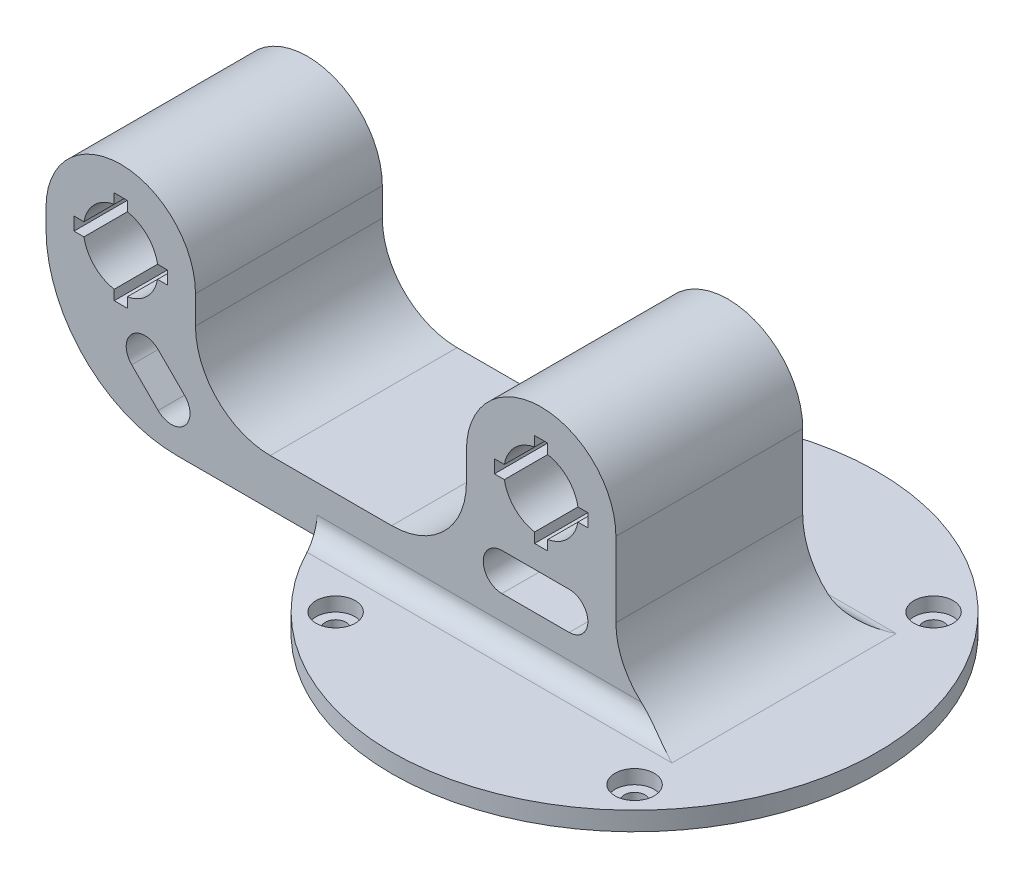
SolidWorks part; units mm, degrees
note: The reader was unsure of these and kept them because the rebuilt part matched: shared geometry of "Эскиз1<3>", "Эскиз1<4>", "Эскиз3<6>", "Эскиз3<7>", "Эскиз4<4>".
ref_plane "Спереди" through (0, 0, 0) normal (0, 0, 1) x (1, 0, 0)
ref_plane "Сверху" through (0, 0, 0) normal (0, 1, 0) x (1, 0, 0)
ref_plane "Справа" through (0, 0, 0) normal (1, 0, 0) x (0, 0, -1)
sketch "Эскиз1" plane through (0, 0, 0) normal (0, 1, 0) x (1, 0, 0)
  line L0 (-16, 0) -> (-16, 16) construction
  line L1 (0, -16) -> (16, -16) construction
  line L2 (-16, 16) -> (0, 16) construction
  line L3 (0, 16) -> (16, 16) construction
  line L4 (16, 16) -> (16, 0) construction
  line L5 (0, 16) -> (0, -16) construction
  line L6 (16, 0) -> (-16, 0) construction
  line L7 (16, 0) -> (16, -16) construction
  line L8 (-16, 0) -> (-16, -16) construction
  line L9 (-16, -16) -> (0, -16) construction
  circle A0 centre (0, 0) radius 24
  circle A1 centre (-16, 16) radius 1.1
  circle A2 centre (16, 16) radius 1.1
  circle A3 centre (16, -16) radius 1.1
  circle A4 centre (-16, -16) radius 1.1
  circle A5 centre (0, 0) radius 26
  dimension "D1" = 48
  dimension "D2" = 2
  dimension "D4" = 2
  dimension "D3" = 2
extrude "Бобышка-Вытянуть1" add sketch "Эскиз1" along normal blind 2 contours A5
extrude "Бобышка-Вытянуть2" add sketch "Эскиз1<3>" against normal blind 1 contours A0
sketch "Эскиз1<3>" plane through (0, 0, 0) normal (0, 1, 0) x (1, 0, 0) same geometry as "Эскиз1"
sketch "Эскиз2" plane through (0, -1, 0) normal (0, -1, 0) x (1, 0, 0)
extrude "Вырез-Вытянуть1" cut sketch "Эскиз1<4>" against normal through all both and the other way through all contours A1 | A4 | A3 | A2
sketch "Эскиз1<4>" plane through (0, 0, 0) normal (0, 1, 0) x (1, 0, 0) same geometry as "Эскиз1"
sketch "Эскиз3" plane through (0, 2, 0) normal (0, 1, 0) x (1, 0, 0)
  line L0 (-37, 10) -> (-53, 10)
  line L1 (8, 10) -> (-8, 10)
  line L2 (8, 10) -> (8, -10)
  line L3 (8, -10) -> (-8, -10)
  line L4 (-8, 10) -> (-8, -10)
  line L5 (0, -10) -> (0, 10) construction
  line L6 (8, 0) -> (-8, 0) construction
  line L7 (-37, 10) -> (-37, -10)
  line L8 (-37, -10) -> (-53, -10)
  line L9 (-53, 10) -> (-53, -10)
  line L10 (-45, -10) -> (-45, 10) construction
  line L11 (-37, 0) -> (-53, 0) construction
  line L12 (-37, -10) -> (-8, -10)
  line L13 (-37, 10) -> (-8, 10)
  circle A0 centre (-16, 16) radius 1.1 construction
  circle A1 centre (-16, -16) radius 1.1 construction
  circle A2 centre (16, -16) radius 1.1 construction
  circle A3 centre (16, 16) radius 1.1 construction
  circle A4 centre (-16, 16) radius 1.1
  circle A5 centre (-16, -16) radius 1.1
  circle A6 centre (16, -16) radius 1.1
  circle A7 centre (16, 16) radius 1.1
  circle A8 centre (16, 16) radius 2.1
  circle A9 centre (16, -16) radius 2.1
  circle A10 centre (-16, -16) radius 2.1
  circle A11 centre (-16, 16) radius 2.1
  point P20 (0, 0)
  point P26 (-45, 0)
  point P42 (-45, 0)
  circle M5 centre (0, 0) radius 26
  dimension "D2" = 4.2
  dimension "D3" = 20
  dimension "D4" = 16
  dimension "D5" = 2
  dimension "D6" = 45
  dimension "D7" = 16
  dimension "D8" = 0
  dimension "D1" = 1
extrude "Вырез-Вытянуть2" cut sketch "Эскиз3" against normal blind 1.5 contours A9 | A8 | A10 | A11
extrude "Бобышка-Вытянуть4" add sketch "Эскиз3<6>" along normal blind 24 contours L0 L9 L8 L7 | L1 L4 L3 L2
sketch "Эскиз3<6>" plane through (0, 2, 0) normal (0, 1, 0) x (1, 0, 0) same geometry as "Эскиз3"
extrude "Бобышка-Вытянуть5" add sketch "Эскиз3<7>" along normal blind 5 contours L13 L7 L12 M5 | L13 L12 L4 M5
sketch "Эскиз3<7>" plane through (0, 2, 0) normal (0, 1, 0) x (1, 0, 0) same geometry as "Эскиз3"
sketch "Эскиз4" plane through (0, 0, 10) normal (0, 0, 1) x (1, 0, 0)
  line L0 (-53, 26) -> (-53, 2) construction
  line L1 (8, 26) -> (8, 2) construction
  line L2 (-37, 7) -> (-8, 7) construction
  line L3 (-37, 26) -> (-37, 7) construction
  line L4 (-53, 2) -> (-24, 2) construction
  line L5 (-42.4142, 9.4142) -> (-39.5858, 6.5858) construction
  line L6 (0.7, 13) -> (-0.7, 13)
  line L7 (-4.2, 8.6) -> (3, 8.6) construction
  line L8 (-41, 10.8284) -> (-38.1716, 8)
  line L9 (-43.8284, 8) -> (-41, 5.1716)
  line L10 (0.7, 13) -> (0.7, 23)
  line L11 (-4.2, 10.6) -> (3, 10.6)
  line L12 (-4.2, 6.6) -> (3, 6.6)
  line L13 (0.7, 23) -> (-0.7, 23)
  line L14 (-0.7, 13) -> (-0.7, 23)
  line L15 (0, 23) -> (0, 13) construction
  line L16 (0.7, 18) -> (-0.7, 18) construction
  line L17 (5, 17.3) -> (-5, 17.3)
  line L18 (5, 17.3) -> (5, 18.7)
  line L19 (5, 18.7) -> (-5, 18.7)
  line L20 (-5, 17.3) -> (-5, 18.7)
  line L21 (0, 18.7) -> (0, 17.3) construction
  line L22 (5, 18) -> (-5, 18) construction
  line L24 (-44.3, 13) -> (-45.7, 13)
  line L25 (-44.3, 13) -> (-44.3, 23)
  line L26 (-44.3, 23) -> (-45.7, 23)
  line L27 (-45.7, 13) -> (-45.7, 23)
  line L28 (-45, 23) -> (-45, 13) construction
  line L29 (-44.3, 18) -> (-45.7, 18) construction
  line L30 (-40, 17.3) -> (-50, 17.3)
  line L31 (-40, 17.3) -> (-40, 18.7)
  line L32 (-40, 18.7) -> (-50, 18.7)
  line L33 (-50, 17.3) -> (-50, 18.7)
  line L34 (-45, 18.7) -> (-45, 17.3) construction
  line L35 (-40, 18) -> (-50, 18) construction
  circle A0 centre (-45, 18) radius 4
  circle A1 centre (0, 18) radius 4
  arc A2 (-53, 18) -> (-37, 18) centre (-45, 18) cw
  arc A3 (-8, 18) -> (8, 18) centre (0, 18) cw
  arc A4 (-39, 2) -> (-53, 16) centre (-39, 16) cw
  arc A5 (-4.2, 10.6) -> (-4.2, 6.6) centre (-4.2, 8.6) ccw
  arc A6 (-41, 10.8284) -> (-43.8284, 8) centre (-42.4142, 9.4142) ccw
  arc A7 (-41, 5.1716) -> (-38.1716, 8) centre (-39.5858, 6.5858) ccw
  arc A8 (3, 6.6) -> (3, 10.6) centre (3, 8.6) ccw
  point P13 (-39, 16)
  point P29 (-41, 8)
  point P38 (-0.6, 8.6)
  line M2 (8, 2) -> (8, 26)
  line M3 (8, 26) -> (-8, 26)
  line M4 (-8, 26) -> (-8, 7)
  line M6 (-37, 7) -> (-37, 26)
  line M7 (-37, 26) -> (-53, 26)
  line M8 (-53, 26) -> (-53, 2)
  line M9 (-53, 2) -> (-24, 2)
  dimension "D1" = 16
  dimension "D4" = 3.6
  dimension "D6" = 14
  dimension "D5" = 14
  dimension "D7" = 2
  dimension "D2" = 2
  dimension "D8" = 4
  dimension "D9" = 2
  dimension "D10" = 6
  dimension "D11" = 1.6
  dimension "D12" = 4
  dimension "D13" = 8.6
  dimension "D14" = 1.4
  dimension "D15" = 10
  dimension "D17" = 10
  dimension "D18" = 19
  dimension "D19" = 19
  dimension "D3" = 2
extrude "Вырез-Вытянуть4" cut sketch "Эскиз4" against normal through all both and the other way through all contours A0 | A2 M8 M7 | A2 M7 M6 | A4 M9 M8 | A3 M4 M3 | A3 M3 M2 | A1 | L19 A1 L17 L14 | A1 L19 L20 L17 | L14 A1 L19 | L10 A1 L14 L19 | L19 A1 L10 | L17 A1 L19 L10 | L10 L19 L14 L17 | L10 A1 L17 | L17 A1 L14 | A1 L10 L13 L14 | A1 L14 L6 L10 | A1 L17 L18 L19 | A0 L25 L26 L27 | L30 A0 L32 L25 | A0 L30 L31 L32 | L25 L32 L27 L30 | L32 A0 L30 L27 | A0 L32 L33 L30 | L27 A0 L25 L30 | L30 A0 L27 | L27 A0 L32 | L32 A0 L25 | L25 A0 L30 | A0 L27 L24 L25
fillet "Скругление2" radius 8 3 edges at (8, 2, 0) (-8, 7, 0) (-37, 7, 0)
fillet "Скругление4" radius 2 2 edges at (-4, 2, -10) (-4, 2, 10)
extrude "Вырез-Вытянуть5" cut sketch "Эскиз4<4>" against normal through all both and the other way through all contours L9 A7 L8 A6 | L12 A8 L11 A5
sketch "Эскиз4<4>" plane through (0, 0, 10) normal (0, 0, 1) x (1, 0, 0) same geometry as "Эскиз4"
